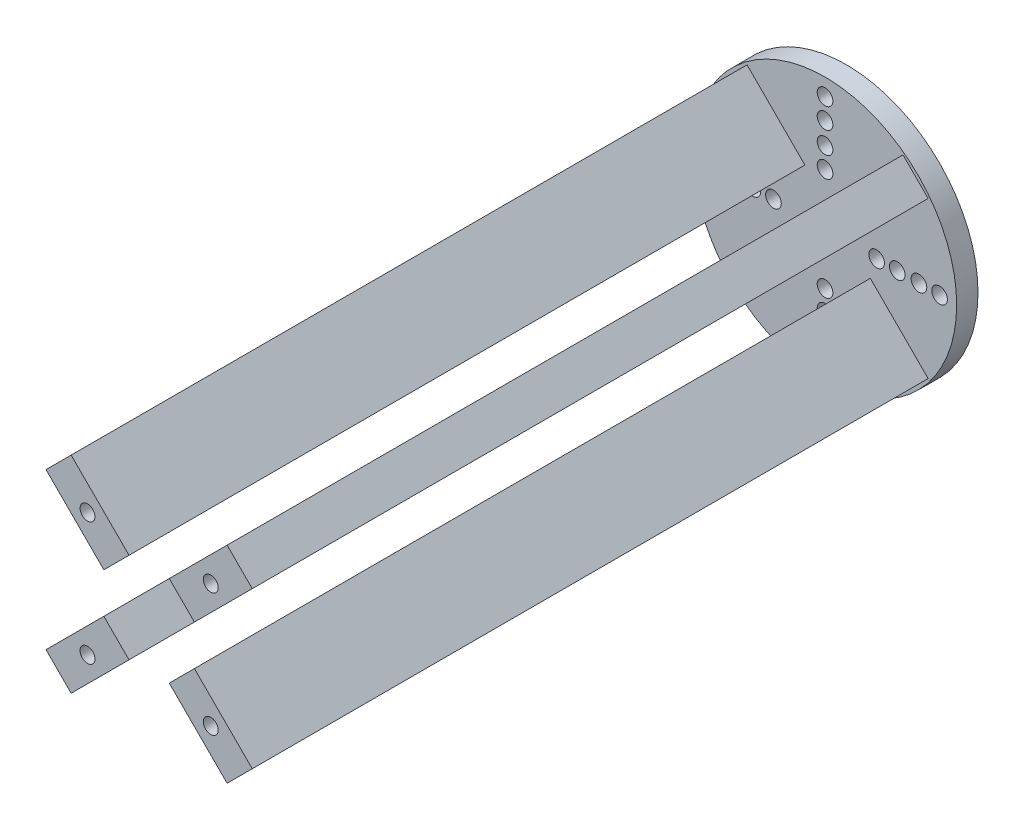
SolidWorks part; units mm, degrees
ref_plane "Ebene vorne" through (0, 0, 0) normal (0, 0, 1) x (1, 0, 0)
ref_plane "Ebene oben" through (0, 0, 0) normal (0, 1, 0) x (1, 0, 0)
ref_plane "Ebene rechts" through (0, 0, 0) normal (1, 0, 0) x (0, 0, -1)
sketch "Skizze2" plane through (0, 0, 0) normal (0, 0, 1) x (1, 0, 0)
  line L0 (0, 18.5) -> (0, -18.5)
  line L1 (-18.5, 0) -> (18.5, 0)
  circle A0 centre (0, 0) radius 18.5
  arc A1 (16.0624, -1.0994) -> (16.0624, 1.0994) centre (0, 0) ccw
  arc A2 (13.1542, -1.099) -> (13.1542, 1.099) centre (0, 0) ccw
  arc A3 (10.0904, -1.0984) -> (10.0904, 1.0984) centre (0, 0) ccw
  arc A4 (7.1666, -1.0968) -> (7.1666, 1.0968) centre (0, 0) ccw
  circle A5 centre (0, 7.25) radius 1.1
  circle A6 centre (0, 10.15) radius 1.1
  circle A7 centre (0, 13.2) radius 1.1
  circle A8 centre (0, 16.1) radius 1.1
  circle A9 centre (7.25, 0) radius 1.1
  circle A10 centre (10.15, 0) radius 1.1
  circle A11 centre (13.2, 0) radius 1.1
  circle A12 centre (16.1, 0) radius 1.1
  circle A13 centre (0, -7.25) radius 1.1
  circle A14 centre (0, -10.15) radius 1.1
  circle A15 centre (0, -13.2) radius 1.1
  circle A16 centre (0, -16.1) radius 1.1
  circle A17 centre (-7.25, 0) radius 1.1
  circle A18 centre (-10.15, 0) radius 1.1
  circle A19 centre (-13.2, 0) radius 1.1
  circle A20 centre (-16.1, 0) radius 1.1
  arc A21 (1.0968, 7.1666) -> (-1.0968, 7.1666) centre (0, 0) ccw
  arc A22 (1.0984, 10.0904) -> (-1.0984, 10.0904) centre (0, 0) ccw
  arc A23 (1.099, 13.1542) -> (-1.099, 13.1542) centre (0, 0) ccw
  arc A24 (1.0994, 16.0624) -> (-1.0994, 16.0624) centre (0, 0) ccw
  arc A25 (-7.1666, 1.0968) -> (-7.1666, -1.0968) centre (0, 0) ccw
  arc A26 (-10.0904, 1.0984) -> (-10.0904, -1.0984) centre (0, 0) ccw
  arc A27 (-13.1542, 1.099) -> (-13.1542, -1.099) centre (0, 0) ccw
  arc A28 (-16.0624, 1.0994) -> (-16.0624, -1.0994) centre (0, 0) ccw
  arc A29 (-1.0968, -7.1666) -> (1.0968, -7.1666) centre (0, 0) ccw
  arc A30 (-1.0984, -10.0904) -> (1.0984, -10.0904) centre (0, 0) ccw
  arc A31 (-1.099, -13.1542) -> (1.099, -13.1542) centre (0, 0) ccw
  arc A32 (-1.0994, -16.0624) -> (1.0994, -16.0624) centre (0, 0) ccw
  point P46 (0, 0)
  dimension "D1" = 37
  dimension "D2" = 32.2
  dimension "D3" = 26.4
  dimension "D4" = 20.3
  dimension "D5" = 14.5
  dimension "D6" = 2.2
  dimension "D7" = 4
extrude "Aufsatz-Linear austragen1" add sketch "Skizze2" along normal blind 3 contours A12 L1 A0 L0 A8 A7 A6 A5 A9 A10 A11 | A16 L0 A0 L1 A12 A11 A10 A9 A13 A14 A15 | A20 L1 A0 L0 A16 A15 A14 A13 A17 A18 A19 | A20 L1 A19 A18 A17 L0 A5 A6 A7 A8 A0 region at (7.9584, 7.9584, 0) region at (-7.9584, 7.9584, 0) region at (7.9584, -7.9584, 0) region at (-7.9584, -7.9584, 0)
sketch "Skizze4" plane through (0, 0, 3) normal (0, 0, 1) x (1, 0, 0)
  line L0 (0, 0) -> (13.0815, 13.0815) construction
  line L1 (2.8284, 6.364) -> (10.9602, 14.4957)
  line L2 (2.8284, 6.364) -> (6.364, 2.8284)
  line L3 (10.9602, 14.4957) -> (14.4957, 10.9602)
  line L4 (6.364, 2.8284) -> (14.4957, 10.9602)
  line L5 (0, 0) -> (18.5, 0) construction
  line L6 (6.364, -2.8284) -> (14.4957, -10.9602)
  line L7 (6.364, -2.8284) -> (2.8284, -6.364)
  line L8 (2.8284, -6.364) -> (10.9602, -14.4957)
  line L9 (14.4957, -10.9602) -> (10.9602, -14.4957)
  line L10 (-2.8284, -6.364) -> (-10.9602, -14.4957)
  line L11 (-2.8284, -6.364) -> (-6.364, -2.8284)
  line L12 (-6.364, -2.8284) -> (-14.4957, -10.9602)
  line L13 (-10.9602, -14.4957) -> (-14.4957, -10.9602)
  line L14 (-6.364, 2.8284) -> (-14.4957, 10.9602)
  line L15 (-6.364, 2.8284) -> (-2.8284, 6.364)
  line L16 (-2.8284, 6.364) -> (-10.9602, 14.4957)
  line L17 (-14.4957, 10.9602) -> (-10.9602, 14.4957)
  circle A0 centre (0, 0) radius 18.5 construction
  point P26 (0, 0)
  dimension "D1" = 2.5
  dimension "D2" = 45
  dimension "D3" = 11.5
  dimension "D4" = 6.5
  dimension "D5" = 2.5
  dimension "D6" = 4
extrude "Aufsatz-Linear austragen2" add sketch "Skizze4" along normal blind 95
sketch "Skizze5" plane through (0, 0, 98) normal (0, 0, 1) x (1, 0, 0)
  line L0 (-6.364, -2.8284) -> (-10.9602, -14.4957) construction
  line L1 (-2.8284, -6.364) -> (-6.364, -2.8284) construction
  line L2 (-6.364, -2.8284) -> (-14.4957, -10.9602) construction
  line L3 (-10.9602, -14.4957) -> (-14.4957, -10.9602) construction
  line L4 (-2.8284, -6.364) -> (-14.4957, -10.9602) construction
  circle A0 centre (-8.6621, -8.6621) radius 1.05
  circle A1 centre (-8.6621, 8.6621) radius 1.05
  circle A2 centre (8.6621, 8.6621) radius 1.05
  circle A3 centre (8.6621, -8.6621) radius 1.05
  point P22 (0, 0)
  dimension "D1" = 2.1
  dimension "D2" = 4
extrude "Schnitt-Linear austragen2" cut sketch "Skizze5" against normal blind 13
